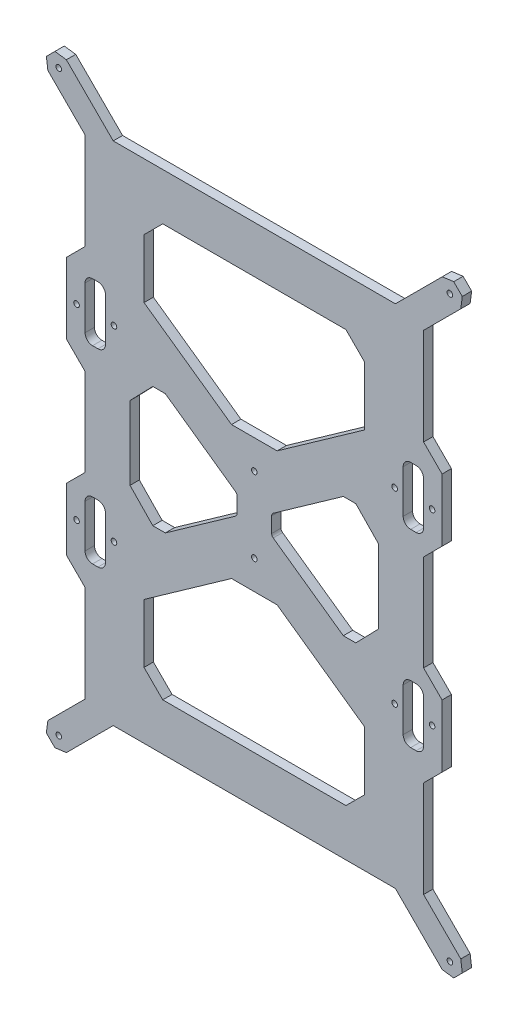
SolidWorks part; units mm, degrees
ref_plane "Piano frontale" through (0, 0, 0) normal (0, 0, 1) x (1, 0, 0)
ref_plane "Piano superiore" through (0, 0, 0) normal (0, 1, 0) x (1, 0, 0)
ref_plane "Piano destro" through (0, 0, 0) normal (1, 0, 0) x (0, 0, -1)
sketch "Schizzo1" plane through (0, 0, 0) normal (0, 0, 1) x (1, 0, 0)
  line L0 (-66.4357, 19.6293) -> (-66.4357, -19.6293)
  line L1 (-86.4486, 39.007) -> (-83.5514, 39.007) construction
  line L2 (-111.1309, 156.5575) -> (-106.5575, 161.1309)
  line L3 (-85, 39.007) -> (-85, 72.1548) construction
  line L4 (-111.1309, 156.5575) -> (-110.3308, 150.4313)
  line L5 (-110.3308, 150.4313) -> (-90.4486, 130.5491)
  line L6 (-90.4486, 130.5491) -> (-90.4486, 78.8741)
  line L7 (-90.4486, 78.8741) -> (-100.3308, 68.992)
  line L8 (-90.4486, 21.1259) -> (-90.4486, -25.6817)
  line L9 (-9.2567, 4.0961) -> (-9.2567, -4.0961)
  line L10 (0, 0) -> (-165.9293, 0) construction
  line L11 (-58.9422, 100.14) -> (-58.9422, 68.7002)
  line L12 (-58.9422, 100.14) -> (-48.9422, 110.14)
  line L13 (-86.4486, 35.007) -> (-83.5514, 35.007)
  line L14 (-75, 50) -> (-107.9533, 50) construction
  line L15 (-79.5514, 39.007) -> (-79.5514, 62.007)
  line L16 (-104.5, 154.5) -> (0, 50) construction
  line L17 (-106.5575, 161.1309) -> (-100.4313, 160.3308)
  line L18 (75, 50) -> (107.9533, 50) construction
  line L19 (85, 39.007) -> (85, 72.1548) construction
  line L20 (86.4486, 39.007) -> (83.5514, 39.007) construction
  line L21 (86.4486, 66.007) -> (83.5514, 66.007)
  line L22 (0, 0) -> (0, 265.525) construction
  line L23 (90.4486, 39.007) -> (90.4486, 62.007)
  line L24 (-100.3308, 68.992) -> (-100.3308, 31.008)
  line L25 (-90.4486, 21.1259) -> (-100.3308, 31.008)
  line L26 (100.4313, 160.3308) -> (75.3933, 135.2928)
  line L27 (47.5638, 32.2218) -> (10.1019, 5.729)
  line L28 (54.2431, 32.2218) -> (47.5638, 32.2218)
  line L29 (-58.9422, 68.7002) -> (-12.1818, 35.6316)
  line L30 (-12.1818, 35.6316) -> (12.1818, 35.6316)
  line L31 (66.4357, 19.6293) -> (54.2431, 32.2218)
  line L32 (58.9422, 68.7002) -> (12.1818, 35.6316)
  line L33 (-75.3933, 135.2928) -> (75.3933, 135.2928)
  line L34 (90.4486, 25.6817) -> (100.3308, 35.5638)
  line L35 (100.3308, 68.992) -> (100.3308, 35.5638)
  line L36 (106.5575, 161.1309) -> (100.4313, 160.3308)
  line L37 (79.5514, 39.007) -> (79.5514, 62.007)
  line L38 (-66.4357, 19.6293) -> (-54.2431, 32.2218)
  line L39 (-54.2431, 32.2218) -> (-47.5638, 32.2218)
  line L40 (-47.5638, 32.2218) -> (-10.1019, 5.729)
  line L41 (86.4486, 35.007) -> (83.5514, 35.007)
  line L42 (58.9422, 100.14) -> (48.9422, 110.14)
  line L43 (58.9422, 100.14) -> (58.9422, 68.7002)
  line L44 (9.2567, 4.0961) -> (9.2567, -4.0961)
  line L45 (90.4486, 25.6817) -> (90.4486, -25.6817)
  line L46 (90.4486, 78.8741) -> (100.3308, 68.992)
  line L47 (90.4486, 130.5491) -> (90.4486, 78.8741)
  line L48 (110.3308, 150.4313) -> (90.4486, 130.5491)
  line L49 (111.1309, 156.5575) -> (110.3308, 150.4313)
  line L50 (111.1309, 156.5575) -> (106.5575, 161.1309)
  line L51 (66.4357, 19.6293) -> (66.4357, -19.6293)
  line L52 (-48.9422, 110.14) -> (48.9422, 110.14)
  line L53 (86.4486, -39.007) -> (83.5514, -39.007) construction
  line L54 (85, -39.007) -> (85, -72.1548) construction
  line L55 (75, -50) -> (107.9533, -50) construction
  line L56 (-75, -50) -> (-107.9533, -50) construction
  line L57 (-85, -39.007) -> (-85, -72.1548) construction
  line L58 (-86.4486, -39.007) -> (-83.5514, -39.007) construction
  line L59 (-86.4486, -66.007) -> (-83.5514, -66.007)
  line L60 (-90.4486, -39.007) -> (-90.4486, -62.007)
  line L61 (-100.4313, -160.3308) -> (-75.3933, -135.2928)
  line L62 (-48.9422, -110.14) -> (48.9422, -110.14)
  line L63 (-100.4313, 160.3308) -> (-75.3933, 135.2928)
  line L64 (111.1309, -156.5575) -> (106.5575, -161.1309)
  line L65 (111.1309, -156.5575) -> (110.3308, -150.4313)
  line L66 (110.3308, -150.4313) -> (90.4486, -130.5491)
  line L67 (90.4486, -130.5491) -> (90.4486, -78.8741)
  line L68 (90.4486, -78.8741) -> (100.3308, -68.992)
  line L69 (58.9422, -100.14) -> (58.9422, -68.7002)
  line L70 (58.9422, -100.14) -> (48.9422, -110.14)
  line L71 (86.4486, -35.007) -> (83.5514, -35.007)
  line L72 (-47.5638, -32.2218) -> (-10.1019, -5.729)
  line L73 (-54.2431, -32.2218) -> (-47.5638, -32.2218)
  line L74 (-90.4486, 39.007) -> (-90.4486, 62.007)
  line L75 (-86.4486, 66.007) -> (-83.5514, 66.007)
  line L76 (-66.4357, -19.6293) -> (-54.2431, -32.2218)
  line L77 (79.5514, -39.007) -> (79.5514, -62.007)
  line L78 (106.5575, -161.1309) -> (100.4313, -160.3308)
  line L79 (100.3308, -68.992) -> (100.3308, -35.5638)
  line L80 (90.4486, -25.6817) -> (100.3308, -35.5638)
  line L81 (-75.3933, -135.2928) -> (75.3933, -135.2928)
  line L82 (58.9422, -68.7002) -> (12.1818, -35.6316)
  line L83 (66.4357, -19.6293) -> (54.2431, -32.2218)
  line L84 (-12.1818, -35.6316) -> (12.1818, -35.6316)
  line L85 (-58.9422, -68.7002) -> (-12.1818, -35.6316)
  line L86 (54.2431, -32.2218) -> (47.5638, -32.2218)
  line L87 (47.5638, -32.2218) -> (10.1019, -5.729)
  line L88 (100.4313, -160.3308) -> (75.3933, -135.2928)
  line L89 (-90.4486, -25.6817) -> (-100.3308, -35.5638)
  line L90 (-100.3308, -68.992) -> (-100.3308, -35.5638)
  line L91 (90.4486, -39.007) -> (90.4486, -62.007)
  line L92 (86.4486, -66.007) -> (83.5514, -66.007)
  line L93 (-106.5575, -161.1309) -> (-100.4313, -160.3308)
  line L94 (-79.5514, -39.007) -> (-79.5514, -62.007)
  line L95 (-86.4486, -35.007) -> (-83.5514, -35.007)
  line L96 (-58.9422, -100.14) -> (-48.9422, -110.14)
  line L97 (-58.9422, -100.14) -> (-58.9422, -68.7002)
  line L98 (-90.4486, -78.8741) -> (-100.3308, -68.992)
  line L99 (-90.4486, -130.5491) -> (-90.4486, -78.8741)
  line L100 (-110.3308, -150.4313) -> (-90.4486, -130.5491)
  line L101 (-111.1309, -156.5575) -> (-110.3308, -150.4313)
  line L102 (-111.1309, -156.5575) -> (-106.5575, -161.1309)
  circle A0 centre (-95, 50) radius 1.5
  circle A1 centre (-75, 50) radius 1.5
  arc A2 (-79.5514, 39.007) -> (-83.5514, 35.007) centre (-83.5514, 39.007) cw
  arc A3 (-83.5514, 66.007) -> (-79.5514, 62.007) centre (-83.5514, 62.007) cw
  arc A4 (9.2567, 4.0961) -> (10.1019, 5.729) centre (11.2567, 4.0961) cw
  arc A5 (90.4486, 39.007) -> (86.4486, 35.007) centre (86.4486, 39.007) cw
  circle A6 centre (-104.5, 154.5) radius 1.5
  arc A7 (86.4486, 66.007) -> (90.4486, 62.007) centre (86.4486, 62.007) cw
  circle A8 centre (104.5, 154.5) radius 1.5
  arc A9 (83.5514, 66.007) -> (79.5514, 62.007) centre (83.5514, 62.007) ccw
  arc A10 (79.5514, 39.007) -> (83.5514, 35.007) centre (83.5514, 39.007) ccw
  circle A11 centre (75, 50) radius 1.5
  circle A12 centre (95, 50) radius 1.5
  arc A13 (-9.2567, -4.0961) -> (-10.1019, -5.729) centre (-11.2567, -4.0961) cw
  arc A14 (-90.4486, -39.007) -> (-86.4486, -35.007) centre (-86.4486, -39.007) cw
  circle A15 centre (0, 20.1313) radius 1.5
  arc A16 (-86.4486, -66.007) -> (-90.4486, -62.007) centre (-86.4486, -62.007) cw
  arc A17 (-86.4486, 66.007) -> (-90.4486, 62.007) centre (-86.4486, 62.007) ccw
  circle A18 centre (0, -20.1313) radius 1.5
  arc A19 (-90.4486, 39.007) -> (-86.4486, 35.007) centre (-86.4486, 39.007) ccw
  circle A20 centre (95, -50) radius 1.5
  circle A21 centre (75, -50) radius 1.5
  arc A22 (79.5514, -39.007) -> (83.5514, -35.007) centre (83.5514, -39.007) cw
  arc A23 (83.5514, -66.007) -> (79.5514, -62.007) centre (83.5514, -62.007) cw
  circle A24 centre (104.5, -154.5) radius 1.5
  arc A25 (86.4486, -66.007) -> (90.4486, -62.007) centre (86.4486, -62.007) ccw
  circle A26 centre (-104.5, -154.5) radius 1.5
  arc A27 (90.4486, -39.007) -> (86.4486, -35.007) centre (86.4486, -39.007) ccw
  arc A28 (9.2567, -4.0961) -> (10.1019, -5.729) centre (11.2567, -4.0961) ccw
  arc A29 (-83.5514, -66.007) -> (-79.5514, -62.007) centre (-83.5514, -62.007) ccw
  arc A30 (-9.2567, 4.0961) -> (-10.1019, 5.729) centre (-11.2567, 4.0961) ccw
  arc A31 (-79.5514, -39.007) -> (-83.5514, -35.007) centre (-83.5514, -39.007) ccw
  circle A32 centre (-75, -50) radius 1.5
  circle A33 centre (-95, -50) radius 1.5
  point P1 (-58.9422, -110.14)
  point P10 (-90.4486, 0)
  point P14 (-85, 35.007)
  point P22 (-85, 66.007)
  point P26 (-108.8442, 158.8442)
  point P66 (-66.4357, 0)
  point P69 (0, 110.14)
  point P72 (-100.3308, 50)
  point P77 (0, 135.2928)
  point P78 (0, 35.6316)
  point P88 (9.2567, 0)
  point P94 (58.9422, 110.14)
  point P96 (108.8442, 158.8442)
  point P97 (85, 66.007)
  point P98 (85, 35.007)
  point P133 (-58.9422, 110.14)
  point P167 (66.4357, 0)
  point P174 (90.4486, 0)
  point P194 (-9.2567, 0)
  point P198 (-66.4357, 0)
  point P199 (85, -35.007)
  point P200 (85, -66.007)
  point P201 (108.8442, -158.8442)
  point P203 (58.9422, -110.14)
  point P204 (0, -35.6316)
  point P205 (0, -135.2928)
  point P207 (0, -110.14)
  point P208 (-108.8442, -158.8442)
  point P209 (-85, -66.007)
  point P210 (-85, -35.007)
  dimension "D1" = 154.5
  dimension "D2" = 104.5
  dimension "D3" = 20
  dimension "D5" = 2
  dimension "D6" = 85
  dimension "D7" = 23
  dimension "D8" = 45
  dimension "D9" = 14
  dimension "D10" = 50
extrude "Estrusione-Estrusione1" add sketch "Schizzo1" against normal blind 5
sketch "Schizzo2" [suppressed] plane through (0, 0, 0) normal (0, 0, 1) x (1, 0, 0)
  line L0 (0, 0) -> (0, 148.2594) construction
  line L1 (58.9422, 84.4201) -> (-108.2298, 84.4201) construction
  line L2 (58.9422, 68.7002) -> (58.9422, 100.14) construction
  line L3 (0, 0) -> (-115.6703, 0) construction
  point P0 (29.4418, 84.4201)
  point P8 (-29.4418, 84.4201)
  point P10 (-55.8026, 0)
  point P12 (-29.4418, 0)
  point P13 (55.8026, 0)
  point P14 (29.4418, 0)
  point P15 (29.4418, -84.4201)
  point P16 (-29.4418, -84.4201)
